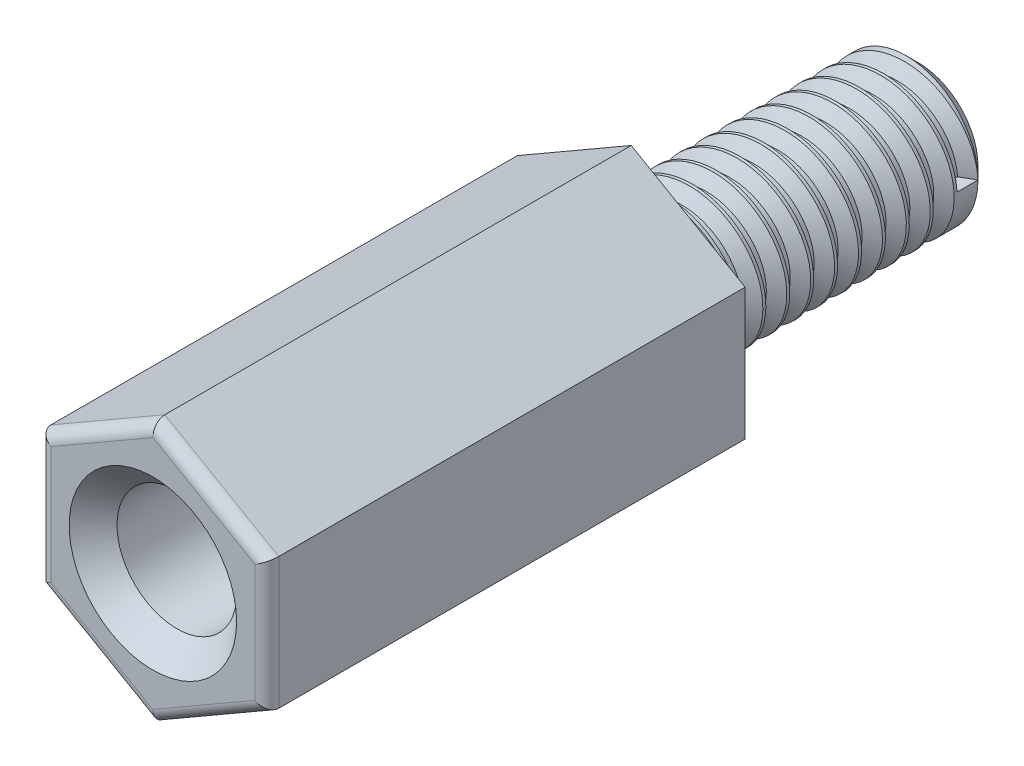
SolidWorks part; units mm, degrees
material "Латунь"
ref_plane "Спереди" through (0, 0, 0) normal (0, 0, 1) x (1, 0, 0)
ref_plane "Сверху" through (0, 0, 0) normal (0, 1, 0) x (1, 0, 0)
ref_plane "Справа" through (0, 0, 0) normal (1, 0, 0) x (0, 0, -1)
sketch "Эскиз1" plane through (0, 0, 0) normal (0, 0, 1) x (1, 0, 0)
  line L1 (0, 2.75) -> (-2.3816, 1.375)
  line L2 (-2.3816, 1.375) -> (-2.3816, -1.375)
  line L3 (-2.3816, -1.375) -> (0, -2.75)
  line L4 (0, -2.75) -> (2.3816, -1.375)
  line L5 (2.3816, -1.375) -> (2.3816, 1.375)
  line L6 (2.3816, 1.375) -> (0, 2.75)
  circle A0 centre (0, 0) radius 2.75 construction
  circle A1 centre (0, 0) radius 2.3816 construction
  dimension "D1" = 5.5
extrude "Бобышка-Вытянуть1" add sketch "Эскиз1" along normal blind 10
sketch "Эскиз2" plane through (0, 0, 0) normal (0, 0, -1) x (-1, 0, 0)
  circle A0 centre (0, 0) radius 1.5
  dimension "D1" = 3
extrude "Бобышка-Вытянуть2" add sketch "Эскиз2" along normal blind 6
hole_wizard "Отверстие обработанное метчиком M31" positions "Эскиз3" profile "Эскиз4" tap size "M3" standard "ISO"
sketch "Эскиз3" plane through (0, 0, 10) normal (0, 0, 1) x (1, 0, 0)
  point P0 (0, 0)
sketch "Эскиз4" plane through (0, 0, 10) normal (1, 0, 0) x (0, -1, 0)
  line L0 (0, 0) -> (0, 9.2511)
  line L1 (0, 9.2511) -> (1.25, 8.5)
  line L2 (1.25, 8.5) -> (1.25, 0.5)
  line L3 (1.25, 0.5) -> (1.75, 0)
  line L5 (1.75, 0) -> (0, 0)
  line L6 (-1.25, 0.5) -> (-1.75, 0) construction
  line L10 (0, 9.2511) -> (-1.25, 8.5) construction
  line L11 (0, -6.35) -> (0, 107.95) construction
  dimension "Диаметр сверла" = 2.5
  dimension "Глубина сверла" = 8.5
  dimension "Диаметр передней зенковки" = 3.5
  dimension "Угол передней зенковки" = 90
  dimension "Угол заточки сверла" = 118
cosmetic thread "Отверстие резьбы2" parameters "D1"=6, "D2"=3
fillet "Скругление1" radius 0.25 6 edges at (1.1908, 2.0625, 10) (2.3816, 0, 10) (1.1908, -2.0625, 10) (-1.1908, -2.0625, 10) (-2.3816, 0, 10) (-1.1908, 2.0625, 10)
chamfer "Фаска1" distance 0.25 angle 45 1 edges at (-1.5, 0, -6)
thread "Резьба1" pitch 0.5 method cut profile "Профиль резьбы1" start angle 0, offset 0, length 6, pitch 0.5, diameter 3
ref_plane "Плоскость1" through (1.5, 0, -5.75) normal (0, -1, 0) x (1, 0, 0)
sketch "Профиль резьбы1" plane through (1.5, 0, -5.75) normal (0, -1, 0) x (1, 0, 0)
  line L0 (0, 0) -> (0, 0.5) construction
  line L11 (0, 0) -> (0, 0.4375)
  line L12 (0, 0.4375) -> (-0.2706, 0.2812)
  line L13 (-0.2706, 0.2812) -> (-0.2706, 0.1562)
  line L15 (-0.2706, 0.1562) -> (0, 0)
  line L17 (-0.2706, 0.2187) -> (0, 0.2187) construction
  point P2 (0, 0)
  dimension "Pitch" = 0.5
  dimension "Profile_Angle" = 60
  dimension "Profile_Land" = 0.125
  dimension "Profile_Height" = 0.2706
